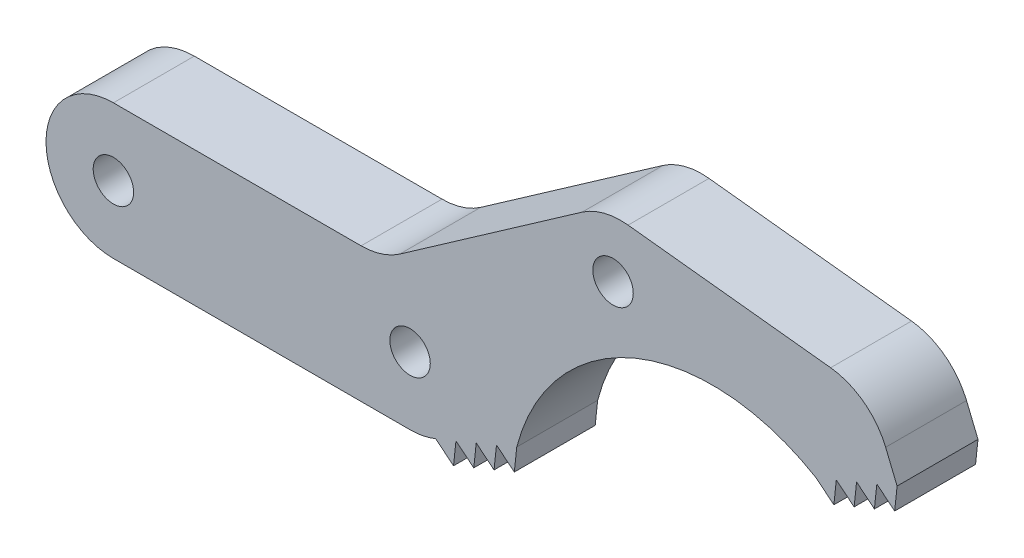
SolidWorks part; units mm, degrees
material "PET"
ref_plane "Front Plane" through (0, 0, 0) normal (0, 0, 1) x (1, 0, 0)
ref_plane "Top Plane" through (0, 0, 0) normal (0, 1, 0) x (1, 0, 0)
ref_plane "Right Plane" through (0, 0, 0) normal (1, 0, 0) x (0, 0, -1)
sketch "Sketch1" plane through (0, 0, 0) normal (0, 0, 1) x (1, 0, 0)
  line L0 (0, 0) -> (22, 0) construction
  line L1 (0, 5) -> (22, 5)
  line L2 (0, -5) -> (22, -5)
  line L3 (19.9443, 5) -> (23.9013, -4.6244) construction
  line L4 (23.9013, -4.6244) -> (58.1218, 9.4454) construction
  line L5 (58.1218, 9.4454) -> (54.1647, 19.0697) construction
  line L6 (54.1647, 19.0697) -> (19.9443, 5) construction
  line L7 (22, 0) -> (56.1433, 14.2576) construction
  line L8 (41.0116, 2.4105) -> (37.0545, 12.0349) construction
  line L9 (52.1101, 6.9736) -> (58.1218, 9.4454) construction
  line L10 (29.913, -2.1527) -> (23.9013, -4.6244) construction
  line L11 (58.1218, 9.4454) -> (56.1433, 14.2576)
  line L12 (19.9443, 5) -> (36.3026, 16.437)
  line L13 (36.3026, 16.437) -> (56.1433, 14.2576)
  line L14 (25.2232, -5.7027) -> (29.732, -3.849) construction
  line L15 (23.9013, -4.6244) -> (25.2232, -5.7027)
  line L16 (25.2232, -5.7027) -> (25.4042, -4.0065)
  line L17 (25.4042, -4.0065) -> (26.7261, -5.0848)
  line L18 (26.7261, -5.0848) -> (26.9072, -3.3885)
  line L19 (26.9072, -3.3885) -> (28.229, -4.4669)
  line L20 (28.229, -4.4669) -> (28.4101, -2.7706)
  line L21 (28.4101, -2.7706) -> (29.732, -3.849)
  line L28 (29.732, -3.849) -> (29.913, -2.1527)
  line L29 (53.432, 5.8953) -> (57.9407, 7.7491) construction
  line L30 (52.1101, 6.9736) -> (53.432, 5.8953)
  line L31 (53.432, 5.8953) -> (53.613, 7.5916)
  line L32 (53.613, 7.5916) -> (54.9349, 6.5132)
  line L33 (54.9349, 6.5132) -> (55.116, 8.2095)
  line L34 (55.116, 8.2095) -> (56.4378, 7.1311)
  line L35 (56.4378, 7.1311) -> (56.6189, 8.8274)
  line L36 (56.6189, 8.8274) -> (57.9407, 7.7491)
  line L37 (57.9407, 7.7491) -> (58.1218, 9.4454)
  line L38 (22, 0) -> (37.424, 10.7837) construction
  arc A0 (0, 5) -> (0, -5) centre (0, 0) ccw
  arc A1 (22, -5) -> (22, 5) centre (22, 0) ccw
  arc A3 (29.913, -2.1527) -> (52.1101, 6.9736) centre (44.4339, -5.9134) cw
  circle A4 centre (0, 0) radius 1.5
  circle A5 centre (22, 0) radius 1.5
  circle A7 centre (37.0545, 12.0349) radius 1.5
  point P3 (11, 0)
  point P21 (38.73, 7.9598)
  dimension "D6" = 6.5
  dimension "D9" = 1.5
  dimension "D8" = 1.5
  dimension "D4" = 157.65
  dimension "D1" = 10
  dimension "D2" = 22
  dimension "D3" = 2.0557
  dimension "D5" = 10.4061
  dimension "D7" = 5.2031
  dimension "34" = 37
extrude "Boss-Extrude1" add sketch "Sketch1" along normal blind 6 contours A1 | A1 L1 A0 L2 A5 A4 region at (11, 0, 0) region at (38.6729, 9.0028, 0)
fillet "Fillet2" radius 5 3 edges at (56.1433, 14.2576, 3) (36.3026, 16.437, 3) (19.9443, 5, 3)
